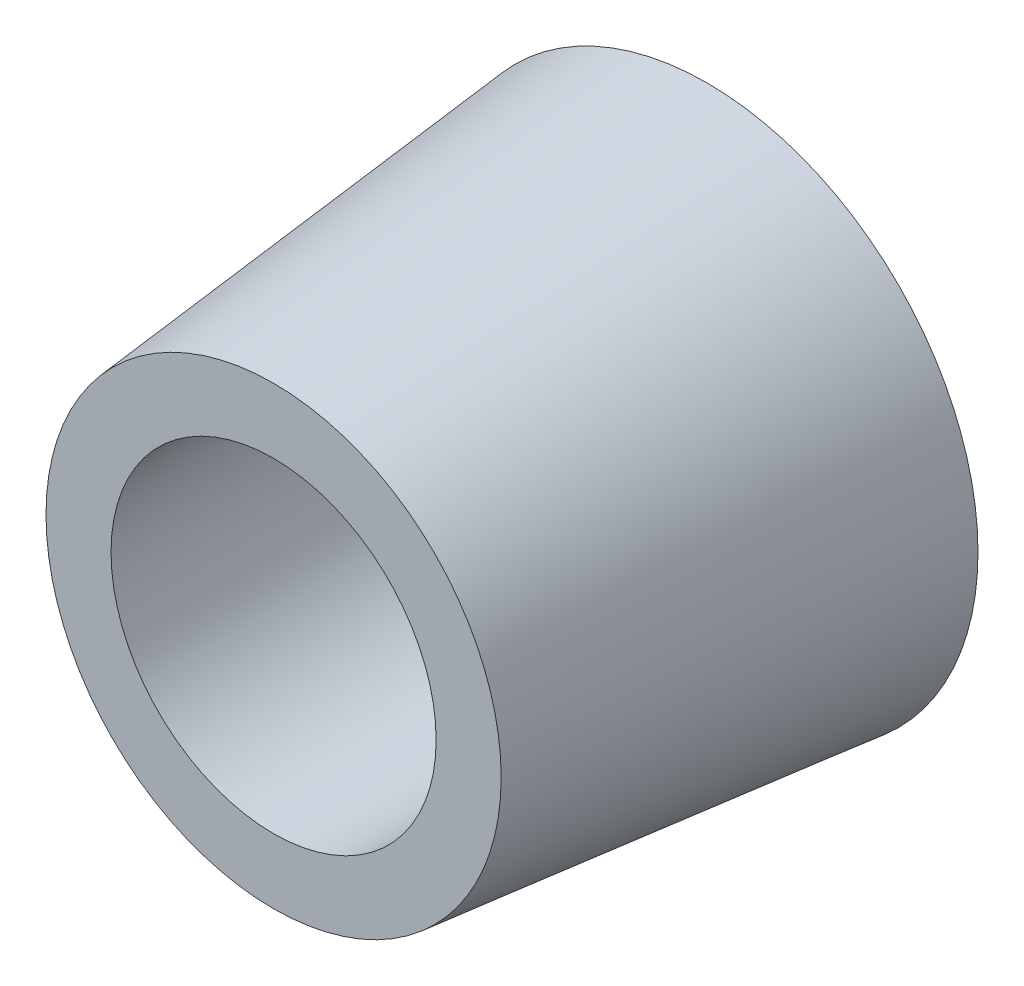
SolidWorks part; units mm, degrees
material "Mosiądz"
ref_plane "Płaszczyzna przednia" through (0, 0, 0) normal (0, 0, 1) x (1, 0, 0)
ref_plane "Płaszczyzna górna" through (0, 0, 0) normal (0, 1, 0) x (1, 0, 0)
ref_plane "Płaszczyzna prawa" through (0, 0, 0) normal (1, 0, 0) x (0, 0, -1)
sketch "Szkic1" plane through (0, 0, 0) normal (0, 0, 1) x (1, 0, 0)
  circle A0 centre (0, 0) radius 2.5
  circle A1 centre (0, 0) radius 1.5
  dimension "D1" = 5
  dimension "D2" = 3
ref_plane "Płaszczyzna1" through (0, 0, 4) normal (0, 0, 1) x (1, 0, 0)
sketch "Szkic2" plane through (0, 0, 4) normal (0, 0, 1) x (1, 0, 0)
  circle A0 centre (0, 0) radius 2.1
  circle A1 centre (0, 0) radius 1.5
  dimension "D1" = 4.2
  dimension "D2" = 3
loft "Wyciągnięcie po profilach1" add section "Szkic1" section "Szkic2" connector at (-2.473, 0.3662, 0) connector at (-2.1, -0.0119, 4)
sketch "Szkic3" plane through (0, 0, 4) normal (0, 0, 1) x (1, 0, 0)
  circle A0 centre (0, 0) radius 1.5
  dimension "D1" = 3
extrude "Wytnij-wyciągnięcie1" cut sketch "Szkic3" against normal blind 10
